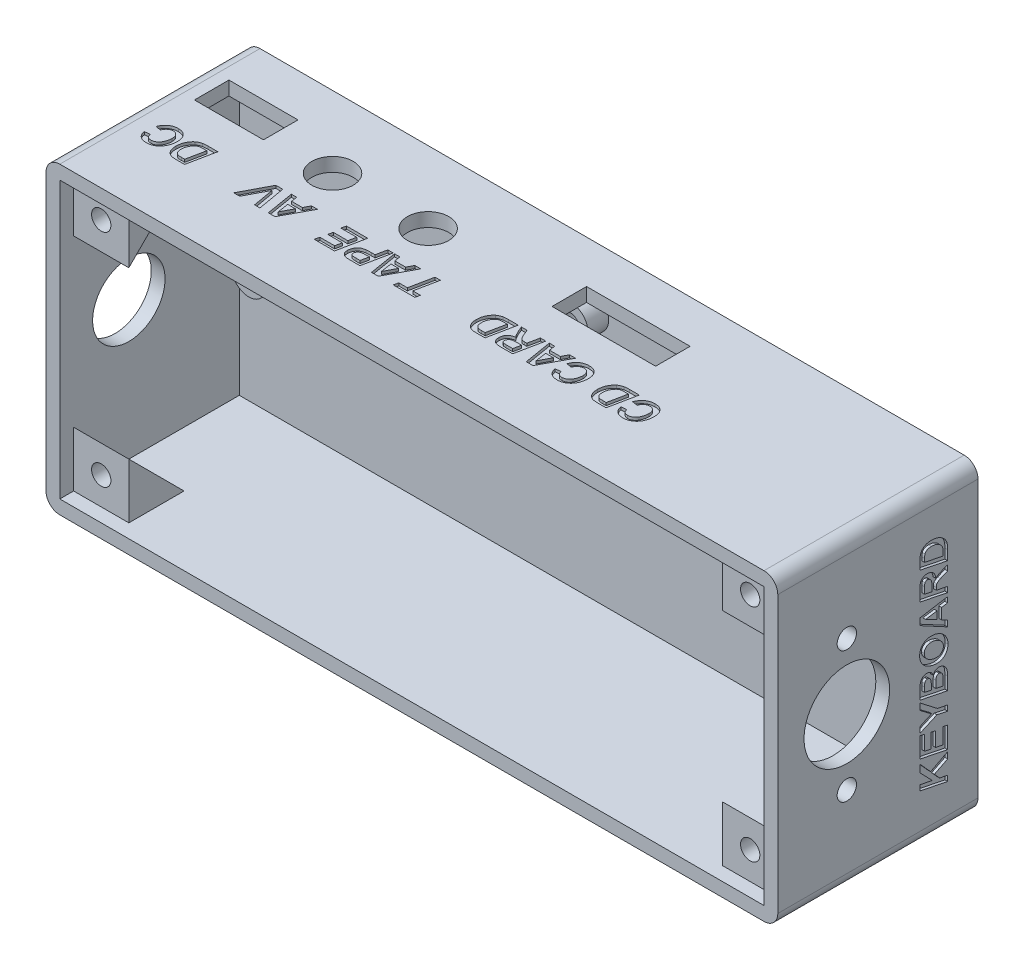
SolidWorks part; units mm, degrees
ref_plane "Спереди" through (0, 0, 0) normal (0, 0, 1) x (1, 0, 0)
ref_plane "Сверху" through (0, 0, 0) normal (0, 1, 0) x (1, 0, 0)
ref_plane "Справа" through (0, 0, 0) normal (1, 0, 0) x (0, 0, -1)
sketch "Эскиз1" plane through (0, 0, 0) normal (0, 0, 1) x (1, 0, 0)
  line L1 (-53, -22) -> (53, -22)
  line L2 (-53, -22) -> (-53, 22)
  line L3 (-53, 22) -> (53, 22)
  line L4 (53, -22) -> (53, 22)
  line L5 (-53, -22) -> (53, 22) construction
  line L6 (-53, 22) -> (53, -22) construction
  point P0 (0, 0)
  dimension "D1" = 106
  dimension "D2" = 44
extrude "Бобышка-Вытянуть1" add sketch "Эскиз1" along normal blind 3
sketch "Эскиз2" plane through (0, 0, 3) normal (0, 0, 1) x (1, 0, 0)
  line L0 (53, 22) -> (-53, 22) construction
  line L1 (-51, -20) -> (51, -20)
  line L2 (-51, -20) -> (-51, 20)
  line L3 (-51, 20) -> (51, 20)
  line L4 (51, -20) -> (51, 20)
  line L5 (-51, -20) -> (51, 20) construction
  line L6 (-51, 20) -> (51, -20) construction
  line L7 (53, -22) -> (53, 22) construction
  line L9 (-53, -22) -> (53, -22)
  line L10 (-53, -22) -> (-53, 22)
  line L11 (-53, 22) -> (53, 22)
  line L12 (53, -22) -> (53, 22)
  line L13 (-53, -22) -> (53, 22) construction
  line L14 (-53, 22) -> (53, -22) construction
  point P0 (0, 0)
  point P10 (0, 0)
  dimension "D1" = 2
  dimension "D2" = 2
extrude "Бобышка-Вытянуть2" add sketch "Эскиз2" along normal blind 26
sketch "Эскиз3" plane through (0, 0, 3) normal (0, 0, 1) x (1, 0, 0)
  line L0 (51, 20) -> (-51, 20) construction
  line L1 (-46.625, -1.47) -> (46.625, -1.47) construction
  line L2 (-46.625, -1.47) -> (-46.625, 16.18) construction
  line L3 (-46.625, 16.18) -> (46.625, 16.18) construction
  line L4 (46.625, -1.47) -> (46.625, 16.18) construction
  line L5 (-46.625, -1.47) -> (46.625, 16.18) construction
  line L6 (-46.625, 16.18) -> (46.625, -1.47) construction
  circle A0 centre (-46.625, -1.47) radius 2.5
  circle A1 centre (46.625, -1.47) radius 2.5
  circle A2 centre (0.005, 16.18) radius 2.5
  point P0 (0, 0)
  point P13 (0, 7.355)
  dimension "D4" = 5
  dimension "D1" = 93.25
  dimension "D2" = 17.65
  dimension "D3" = 46.63
  dimension "D5" = 3.82
extrude "Бобышка-Вытянуть3" add sketch "Эскиз3" along normal blind 3
sketch "Эскиз4" plane through (0, 0, 6) normal (0, 0, 1) x (1, 0, 0)
  circle A0 centre (-46.625, -1.47) radius 1.15
  circle A1 centre (0.005, 16.18) radius 1.15
  circle A2 centre (46.625, -1.47) radius 1.15
  dimension "D1" = 2.3
extrude "Вырез-Вытянуть1" cut sketch "Эскиз4" against normal blind 5.6
sketch "Эскиз5" plane through (0, 22, 0) normal (0, 1, 0) x (1, 0, 0)
  line L1 (-49.3, -6.2) -> (-39.3, -6.2)
  line L2 (-49.3, -6.2) -> (-49.3, -11.2)
  line L3 (-49.3, -11.2) -> (-39.3, -11.2)
  line L4 (-39.3, -6.2) -> (-39.3, -11.2)
  line L5 (-49.3, -6.2) -> (-39.3, -11.2) construction
  line L6 (-49.3, -11.2) -> (-39.3, -6.2) construction
  line L7 (2.5, -6.2) -> (17.5, -6.2)
  line L8 (2.5, -6.2) -> (2.5, -11.2)
  line L9 (2.5, -11.2) -> (17.5, -11.2)
  line L10 (17.5, -6.2) -> (17.5, -11.2)
  line L11 (2.5, -6.2) -> (17.5, -11.2) construction
  line L12 (2.5, -11.2) -> (17.5, -6.2) construction
  line L13 (53, 0) -> (-53, 0) construction
  line L14 (-53, -29) -> (-53, 0) construction
  circle A0 centre (-30.1, -10.4) radius 3
  circle A1 centre (-16.25, -10.4) radius 3
  point P0 (-44.3, -8.7)
  point P9 (10, -8.7)
  dimension "D5" = 6
  dimension "D2" = 10
  dimension "D3" = 6.2
  dimension "D4" = 5
  dimension "D6" = 13.85
  dimension "D7" = 14.2
  dimension "D8" = 26.25
  dimension "D9" = 10.4
  dimension "D10" = 5
  dimension "D11" = 15
  dimension "D12" = 22.9
extrude "Вырез-Вытянуть2" cut sketch "Эскиз5" against normal up to next
sketch "Эскиз7" plane through (53, 0, 0) normal (1, 0, 0) x (0, 0, -1)
  line L0 (-20, 0) -> (-6.0564, 0) construction
  line L1 (-29, -22) -> (-29, 22) construction
  circle A0 centre (-19, 0) radius 6.2
  circle A1 centre (-19, -9.5) radius 1.4
  circle A2 centre (-19, 9.5) radius 1.4
  dimension "D1" = 12.4
  dimension "D4" = 2.8
  dimension "D2" = 10
  dimension "D3" = 19
extrude "Вырез-Вытянуть3" cut sketch "Эскиз7" against normal up to next
sketch "Эскиз8" plane through (51, 0, 0) normal (-1, 0, 0) x (0, 0, 1)
  line L0 (27, 20) -> (27, 12)
  line L1 (29, 20) -> (3, 20) construction
  line L2 (27, 12) -> (19, 20)
  line L3 (19, 20) -> (27, 20)
  line L4 (29, -20) -> (29, 20) construction
  dimension "D1" = 8
  dimension "D2" = 8
  dimension "D3" = 2
extrude "Бобышка-Вытянуть4" add sketch "Эскиз8" along normal blind 8
sketch "Эскиз9" plane through (0, 0, 27) normal (0, 0, 1) x (1, 0, 0)
  line L0 (43, 12) -> (43, 20) construction
  line L1 (43, 20) -> (51, 20) construction
  line L2 (43, 20) -> (43, 12) construction
  line L3 (43, 12) -> (51, 12) construction
  line L4 (51, 20) -> (51, 12) construction
  line L5 (43, 20) -> (51, 12) construction
  line L6 (43, 12) -> (51, 20) construction
  line L7 (43, 20) -> (51, 20) construction
  circle A0 centre (47, 16) radius 1.4
  point P0 (47, 16)
  dimension "D1" = 2.8
extrude "Вырез-Вытянуть4" cut sketch "Эскиз9" against normal up to next
mirror "Зеркальное отражение1" about plane through (0, 0, 0) normal (0, 1, 0) of "Вырез-Вытянуть4", "Бобышка-Вытянуть4"
mirror "Зеркальное отражение2" about plane through (0, 0, 0) normal (1, 0, 0) of "Вырез-Вытянуть4", "Зеркальное отражение1", "Бобышка-Вытянуть4"
fillet "Скругление1" radius 2 4 edges at (-53, 22, 14.5) (53, 22, 14.5) (53, -22, 14.5) (-53, -22, 14.5)
sketch "Эскиз10" plane through (0, 22, 0) normal (0, 1, 0) x (1, 0, 0)
  line L0 (51, 0) -> (-51, 0) construction
  line L1 (-53, -29) -> (-53, 0) construction
  text T0 "<r180>VA</r>" font "Times New Roman" height 4
  text T1 "<r180>EPAT</r>" font "Times New Roman" height 4
  text T2 "<r180>CD</r>" font "Times New Roman" height 4
  text T3 "<r180>DRAC DC</r>" font "Times New Roman" height 4
  dimension "D1" = 16
  dimension "D2" = 22.5962
  dimension "D3" = 11.2585
  dimension "D4" = 14.4528
  dimension "D5" = 21.8
extrude "Вырез-Вытянуть5" cut sketch "Эскиз10" against normal blind 0.4
sketch "Эскиз11" plane through (53, 0, 0) normal (1, 0, 0) x (0, 0, -1)
  line L0 (-4.4, -16) -> (-4.4, 15) construction
  line L1 (0, -20) -> (0, 20) construction
  line L2 (0, -22) -> (-29, -22) construction
  text T0 "KEYBOARD" font "Arial" height 4
  dimension "D1" = 4.4
  dimension "D2" = 31
  dimension "D3" = 6
extrude "Вырез-Вытянуть6" cut sketch "Эскиз11" against normal blind 0.4
sketch "Эскиз12" plane through (0, 20, 0) normal (0, -1, 0) x (1, 0, 0)
  line L1 (-53, 0) -> (-53, 29) construction
  line L2 (-51, 0) -> (51, 0) construction
  text T0 "© Peter Ukhov 2023" font "Arial" height 6
  dimension "D1" = 16
  dimension "D2" = 14
sketch "Эскиз13" plane through (-53, 0, 0) normal (-1, 0, 0) x (0, 0, 1)
  line L0 (29, 20) -> (29, -20) construction
  circle A0 centre (19, 0) radius 5.25
  point P2 (18.1363, 0)
  point P5 (19.6736, 0)
  dimension "D1" = 10.5
  dimension "D2" = 10
extrude "Вырез-Вытянуть8" cut sketch "Эскиз13" against normal up to next
sketch "Эскиз14" plane through (-53, 0, 0) normal (-1, 0, 0) x (0, 0, 1)
  line L0 (6.2274, 10.1387) -> (6.2274, -12.1287) construction
  text T0 "POWER" font "Arial" height 4
  point P3 (6.2274, 10.1387)
  point P4 (0, 0)
extrude "Вырез-Вытянуть9" cut sketch "Эскиз14" against normal blind 0.4
extrude "Вырез-Вытянуть10" cut sketch "Эскиз12" against normal blind 0.4
equation "\"D1@Эскиз1\"=100+2*2+2"
equation "\"D2@Эскиз1\"=40+2*2"
equation "\"D5@Эскиз3\"=3.42+0.4"
equation "\"D2@Эскиз7\"=14/2+3"
